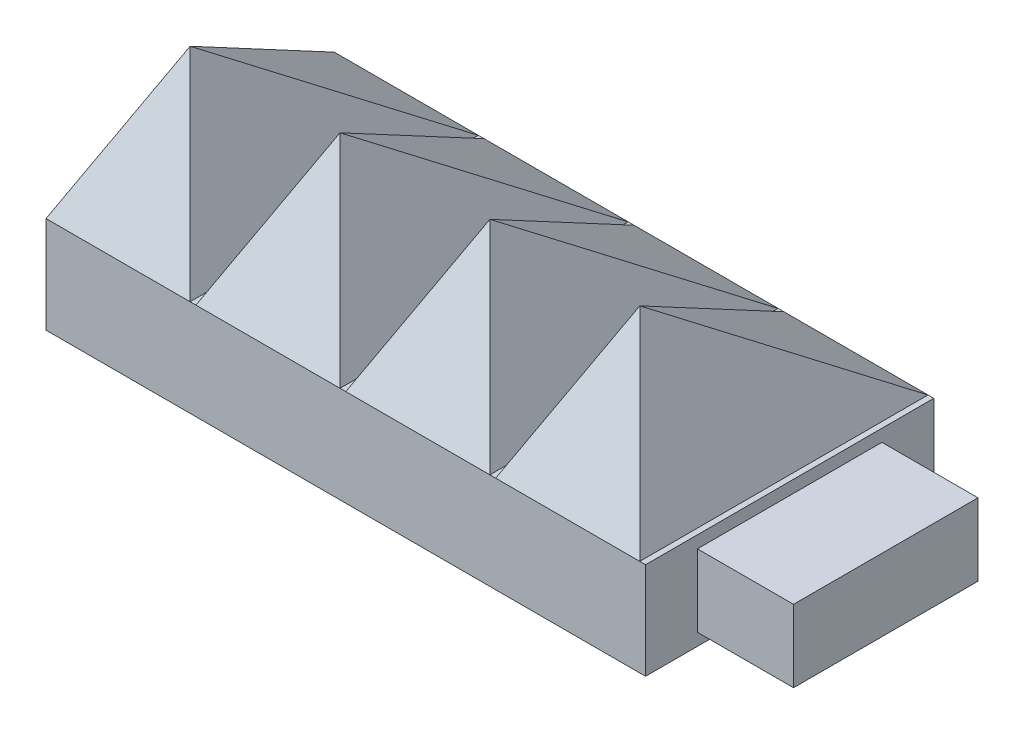
SolidWorks part; units mm, degrees
ref_plane "Front Plane" through (0, 0, 0) normal (0, 0, 1) x (1, 0, 0)
ref_plane "Top Plane" through (0, 0, 0) normal (0, 1, 0) x (1, 0, 0)
ref_plane "Right Plane" through (0, 0, 0) normal (1, 0, 0) x (0, 0, -1)
sketch "Sketch1" plane through (0, 0, 0) normal (0, 1, 0) x (1, 0, 0)
  line L1 (0, 0) -> (19.05, 0)
  line L2 (0, 0) -> (0, -19.05)
  line L3 (0, -19.05) -> (19.05, -19.05)
  line L4 (19.05, 0) -> (19.05, -19.05)
extrude "Boss-Extrude2" add sketch "Sketch1" along normal blind 6.35
ref_plane "Plane2" through (0, 26.0731, 0) normal (0, 1, 0) x (1, 0, 0)
sketch "Sketch8" plane through (0, 0, 0) normal (0, 1, 0) x (1, 0, 0)
  line L9 (0, 9.525) -> (217.17, 9.525)
  line L10 (0, 9.525) -> (0, -28.575)
  line L11 (0, -28.575) -> (217.17, -28.575)
  line L12 (217.17, 9.525) -> (217.17, -28.575)
extrude "Boss-Extrude4" add sketch "Sketch8" along normal blind 6.35 contours L11 L12 L9 L10
extrude "Boss-Extrude5" add sketch "Sketch8<5>" against normal blind 6.4262 contours L11 L12 L9 L10
sketch "Sketch8<5>" plane through (0, 0, 0) normal (0, 1, 0) x (1, 0, 0) same geometry as "Sketch8"
sketch "Sketch9" plane through (0, 6.35, 0) normal (0, 1, 0) x (1, 0, 0)
  line L0 (0, -28.575) -> (217.17, -28.575) construction
  line L1 (0, 9.525) -> (19.05, 9.525)
  line L2 (0, 9.525) -> (0, -28.575)
  line L3 (0, -28.575) -> (19.05, -28.575)
  line L4 (19.05, 9.525) -> (19.05, -28.575)
sketch "Sketch13" plane through (0, 6.35, 0) normal (0, 1, 0) x (1, 0, 0)
  line L0 (0, -9.525) -> (19.05, -28.575)
  line L1 (0, 9.525) -> (0, -28.575) construction
  line L2 (19.05, -28.575) -> (19.05, -9.525)
  line L3 (19.05, 9.525) -> (19.05, -28.575) construction
  line L4 (19.05, -9.525) -> (0, -28.575)
ref_plane "Plane4" through (0, 26.0731, 0) normal (0, 1, 0) x (1, 0, 0)
sketch "Sketch14" plane through (0, 26.0731, 0) normal (0, 1, 0) x (1, 0, 0)
  line L0 (0, -9.525) -> (19.05, -28.575) construction
  point P0 (9.525, -19.05)
loft "Loft3" add profiles "Sketch9", "Sketch14"
pattern_linear "LPattern3" count 11 spacing 19.812 along (1, 0, 0) of "Loft3"
sketch "Sketch15" plane through (0, -6.4262, 0) normal (0, -1, 0) x (1, 0, 0)
  line L0 (217.17, -9.525) -> (217.17, 28.575) construction
  line L1 (0, -9.525) -> (0, 28.575) construction
  circle A0 centre (179.07, 9.525) radius 12.192
  circle A1 centre (38.1, 9.525) radius 12.192
  circle A2 centre (108.585, 9.525) radius 12.192
  dimension "D1" = 38.1
  dimension "D2" = 70.485
  dimension "D3" = 38.1
  dimension "D4" = 24.384
  dimension "D5" = 24.384
  dimension "D6" = 24.384
extrude "Boss-Extrude6" add sketch "Sketch15" along normal blind 6.35
sketch "Sketch16" plane through (217.17, 0, 0) normal (1, 0, 0) x (0, 0, -1)
  line L1 (-38.7442, 27.3065) -> (18.521, 27.3065)
  line L2 (-38.7442, 27.3065) -> (-38.7442, -14.986)
  line L3 (-38.7442, -14.986) -> (18.521, -14.986)
  line L4 (18.521, 27.3065) -> (18.521, -14.986)
extrude "Cut-Extrude1" cut sketch "Sketch16" against normal up to vertex (137.922 mm away) up to point (79.248, 6.35, -9.525)
sketch "Sketch17" plane through (79.248, 0, 0) normal (1, 0, 0) x (0, 0, -1)
  line L4 (-21.717, 4.7371) -> (2.667, 4.7371)
  line L5 (-21.717, 4.7371) -> (-21.717, -4.8133)
  line L6 (-21.717, -4.8133) -> (2.667, -4.8133)
  line L7 (2.667, 4.7371) -> (2.667, -4.8133)
  line L8 (-21.717, 4.7371) -> (2.667, -4.8133) construction
  line L9 (-21.717, -4.8133) -> (2.667, 4.7371) construction
  point P6 (-9.525, -0.0381)
  dimension "D1" = 9.5504
  dimension "D2" = 24.384
extrude "Boss-Extrude7" add sketch "Sketch17" along normal blind 12.7
